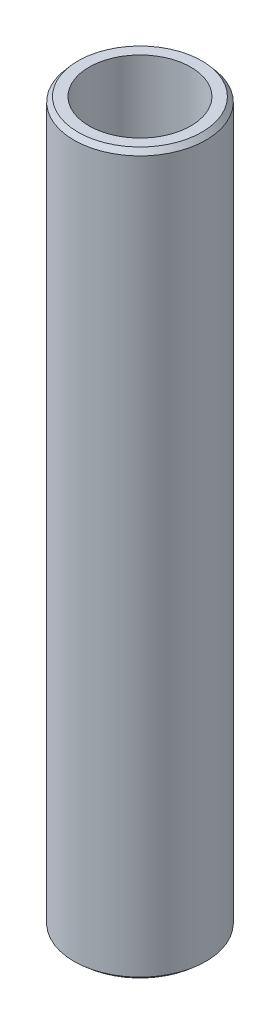
SolidWorks part; units mm, degrees
ref_plane "Front Plane" through (0, 0, 0) normal (0, 0, 1) x (1, 0, 0)
ref_plane "Top Plane" through (0, 0, 0) normal (0, 1, 0) x (1, 0, 0)
ref_plane "Right Plane" through (0, 0, 0) normal (1, 0, 0) x (0, 0, -1)
sketch "Sketch1" plane through (0, 0, 0) normal (0, 1, 0) x (1, 0, 0)
  circle A0 centre (0, 0) radius 55
  dimension "SHAFT_OD" = 110
extrude "Boss-Extrude1" add sketch "Sketch1" along normal blind 600
sketch "Sketch2" plane through (0, 0, 0) normal (0, 1, 0) x (1, 0, 0)
  circle A0 centre (0, 0) radius 42.4289
  dimension "BORE_D" = 84.8579
extrude "Cut-Extrude1" cut sketch "Sketch2" along normal through all
chamfer "Chamfer1" distance 3.9921 angle 40.858 2 edges at (0, 600, 55) (0, 0, 55) first distance on face at (0, 600, 55) first distance on face at (0, 0, 42.4289)
